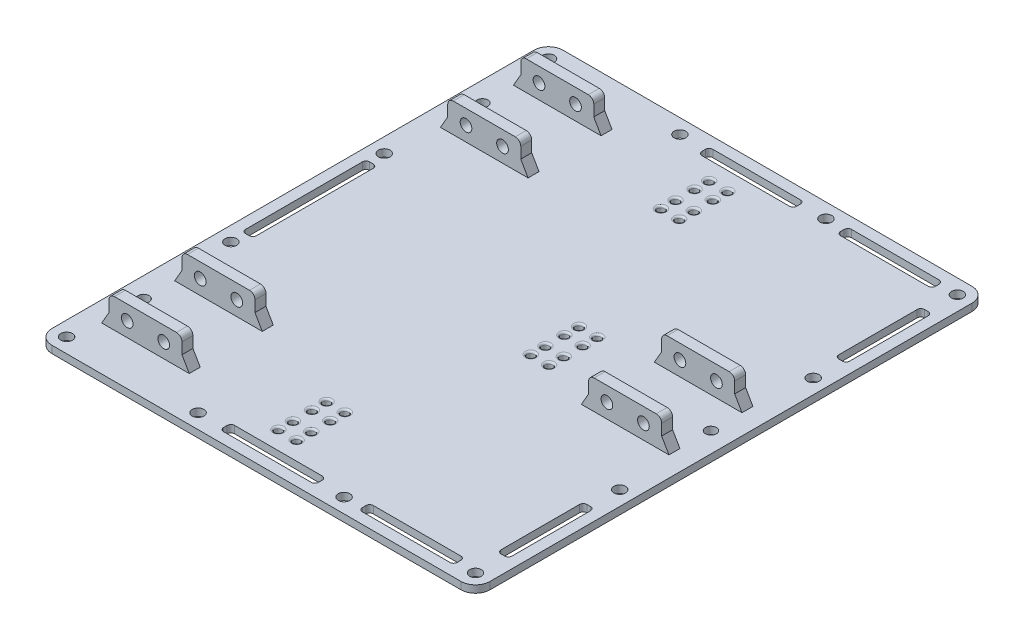
SolidWorks part; units mm, degrees
ref_plane "Front Plane" through (0, 0, 0) normal (0, 0, 1) x (1, 0, 0)
ref_plane "Top Plane" through (0, 0, 0) normal (0, 1, 0) x (1, 0, 0)
ref_plane "Right Plane" through (0, 0, 0) normal (1, 0, 0) x (0, 0, -1)
sketch "Sketch1" plane through (0, 0, 0) normal (0, 1, 0) x (1, 0, 0)
  line L1 (-60, -70) -> (60, -70)
  line L2 (-60, -70) -> (-60, 70)
  line L3 (-60, 70) -> (60, 70)
  line L4 (60, -70) -> (60, 70)
  line L5 (-60, -70) -> (60, 70) construction
  line L6 (-60, 70) -> (60, -70) construction
  point P0 (0, 0)
  dimension "D1" = 120
  dimension "D2" = 140
extrude "Boss-Extrude1" add sketch "Sketch1" along normal blind 2
sketch "Sketch3" plane through (0, 2, 0) normal (0, 1, 0) x (1, 0, 0)
  line L0 (-60, -70) -> (60, -70) construction
  line L1 (-52.5, 57.9) -> (-32.5, 57.9)
  line L2 (-52.5, 57.9) -> (-52.5, 54.9)
  line L3 (-52.5, 54.9) -> (-32.5, 54.9)
  line L4 (-32.5, 57.9) -> (-32.5, 54.9)
  line L5 (-52.5, 37.9) -> (-32.5, 37.9)
  line L6 (-52.5, 37.9) -> (-52.5, 34.9)
  line L7 (-52.5, 34.9) -> (-32.5, 34.9)
  line L8 (-32.5, 37.9) -> (-32.5, 34.9)
  line L9 (-52.5, -34.9) -> (-32.5, -34.9)
  line L10 (-52.5, -34.9) -> (-52.5, -37.9)
  line L11 (-52.5, -37.9) -> (-32.5, -37.9)
  line L12 (-32.5, -34.9) -> (-32.5, -37.9)
  line L13 (-52.5, -54.9) -> (-32.5, -54.9)
  line L14 (-52.5, -54.9) -> (-52.5, -57.9)
  line L15 (-52.5, -57.9) -> (-32.5, -57.9)
  line L16 (-32.5, -54.9) -> (-32.5, -57.9)
  line L17 (32.5, 11.5) -> (52.5, 11.5)
  line L18 (32.5, 11.5) -> (32.5, 8.5)
  line L19 (32.5, 8.5) -> (52.5, 8.5)
  line L20 (52.5, 11.5) -> (52.5, 8.5)
  line L21 (32.5, -8.5) -> (52.5, -8.5)
  line L22 (32.5, -8.5) -> (32.5, -11.5)
  line L23 (32.5, -11.5) -> (52.5, -11.5)
  line L24 (52.5, -8.5) -> (52.5, -11.5)
  line L25 (-60, 70) -> (-60, -70) construction
  line L26 (60, 70) -> (-60, 70) construction
  line L27 (60, -70) -> (60, 70) construction
  dimension "D1" = 12.1
  dimension "D2" = 3
  dimension "D3" = 7.5
  dimension "D4" = 27.5
  dimension "D5" = 7.5
  dimension "D6" = 27.5
  dimension "D7" = 3
  dimension "D8" = 32.1
  dimension "D9" = 12.1
  dimension "D10" = 3
  dimension "D11" = 7.5
  dimension "D12" = 27.5
  dimension "D13" = 32.1
  dimension "D14" = 3
  dimension "D15" = 7.5
  dimension "D16" = 27.5
  dimension "D17" = 7.5
  dimension "D18" = 27.5
  dimension "D19" = 3
  dimension "D20" = 8.5
  dimension "D21" = 7.5
  dimension "D22" = 27.5
  dimension "D23" = 3
  dimension "D24" = 8.5
extrude "Boss-Extrude2" add sketch "Sketch3" along normal blind 8
sketch "Sketch4" plane through (0, 0, 57.9) normal (0, 0, 1) x (1, 0, 0)
  line L0 (-60, 2) -> (60, 2) construction
  line L1 (-60, 2) -> (-60, 0) construction
  line L2 (60, 2) -> (60, 0) construction
  line L3 (32.5, 2) -> (52.5, 2) construction
  circle A0 centre (-47.5, 6) radius 1.6
  circle A1 centre (-37.5, 6) radius 1.6
  circle A2 centre (37.5, 6) radius 1.6
  circle A3 centre (47.5, 6) radius 1.6
  dimension "D3" = 3.2
  dimension "D6" = 3.2
  dimension "D7" = 3.2
  dimension "D12" = 3.2
  dimension "D1" = 4
  dimension "D2" = 12.5
  dimension "D4" = 10
  dimension "D5" = 4
  dimension "D8" = 12.5
  dimension "D9" = 4
  dimension "D10" = 4
  dimension "D11" = 22.5
extrude "Cut-Extrude2" cut sketch "Sketch4" against normal through all
sketch "Sketch5" plane through (0, 2, 0) normal (0, 1, 0) x (1, 0, 0)
  line L0 (-60, -70) -> (60, -70) construction
  line L1 (-60, 70) -> (-60, -70) construction
  line L2 (60, -70) -> (60, 70) construction
  line L3 (60, 70) -> (-60, 70) construction
  circle A0 centre (-56, -66) radius 1.6
  circle A1 centre (56, -66) radius 1.6
  circle A2 centre (56, 66) radius 1.6
  circle A3 centre (-56, 66) radius 1.6
  circle A6 centre (-56, -21) radius 1.6
  circle A7 centre (-56, 21) radius 1.6
  circle A8 centre (-20, -66) radius 1.6
  circle A9 centre (-20, 66) radius 1.6
  circle A10 centre (20, -66) radius 1.6
  circle A11 centre (20, 66) radius 1.6
  circle A12 centre (56, -26.5) radius 1.6
  circle A13 centre (56, 26.5) radius 1.6
  dimension "D1" = 3.2
  dimension "D2" = 3.2
  dimension "D3" = 3.2
  dimension "D6" = 3.2
  dimension "D13" = 40
  dimension "D16" = 4
  dimension "D20" = 3.2
  dimension "D22" = 3.2
  dimension "D25" = 3.2
  dimension "D28" = 3.2
  dimension "D31" = 3.2
  dimension "D7" = 3.2
  dimension "D10" = 3.2
  dimension "D29" = 3.2
  dimension "D4" = 4
  dimension "D5" = 4
  dimension "D8" = 4
  dimension "D9" = 4
  dimension "D11" = 4
  dimension "D12" = 4
  dimension "D14" = 40
  dimension "D15" = 40
  dimension "D17" = 4
  dimension "D19" = 4
  dimension "D21" = 4
  dimension "D23" = 49
  dimension "D24" = 49
  dimension "D26" = 43.5
  dimension "D32" = 40
  dimension "D33" = 43.5
  dimension "D34" = 4
extrude "Cut-Extrude3" cut sketch "Sketch5" against normal through all
fillet "Fillet1" radius 4 4 edges at (60, 1, -70) (-60, 1, -70) (-60, 1, 70) (60, 1, 70)
sketch "Sketch6" plane through (0, 0, 0) normal (0, -1, 0) x (1, 0, 0)
  line L0 (0, 55) -> (0, 49.8) construction
  line L1 (0, 0) -> (-60, 0) construction
  line L2 (56, -70) -> (-56, -70) construction
  line L3 (-5, -49.8) -> (-5, -55) construction
  line L4 (-60, -66) -> (-60, 66) construction
  line L5 (0, -49.8) -> (0, -55) construction
  line L6 (-5, 49.8) -> (-5, 55) construction
  line L7 (60, 66) -> (60, -66) construction
  line L8 (-56, 70) -> (56, 70) construction
  line L9 (16.75, 2.6) -> (16.75, -2.6) construction
  line L10 (11.75, 2.6) -> (11.75, -2.6) construction
  circle A0 centre (0, 59) radius 1
  circle A1 centre (0, 49.8) radius 1
  circle A8 centre (0, 45.8) radius 1
  circle A9 centre (0, 55) radius 1
  circle A10 centre (0, 45.8) radius 1
  circle A11 centre (0, 55) radius 1
  circle A13 centre (0, -49.8) radius 1
  circle A14 centre (0, -55) radius 1
  circle A16 centre (0, -45.8) radius 1
  circle A17 centre (0, -59) radius 1
  circle A24 centre (-5, -49.8) radius 1
  circle A25 centre (-5, -55) radius 1
  circle A26 centre (-5, -45.8) radius 1
  circle A27 centre (-5, -59) radius 1
  circle A28 centre (-5, 59) radius 1
  circle A29 centre (-5, 45.8) radius 1
  circle A30 centre (-5, 55) radius 1
  circle A31 centre (-5, 49.8) radius 1
  circle A32 centre (16.75, 2.6) radius 1
  circle A33 centre (16.75, -2.6) radius 1
  circle A34 centre (16.75, 6.6) radius 1
  circle A35 centre (16.75, -6.6) radius 1
  circle A36 centre (11.75, 2.6) radius 1
  circle A37 centre (11.75, -2.6) radius 1
  circle A38 centre (11.75, 6.6) radius 1
  circle A39 centre (11.75, -6.6) radius 1
  point P6 (16.75, 0)
  point P8 (0, -52.4)
  point P9 (0, 52.4)
  point P49 (-5, -52.4)
  point P77 (0, 0)
  point P78 (11.75, 0)
  point P87 (0, 0)
  dimension "D1" = 2
  dimension "D2" = 2
  dimension "D10" = 43.25
  dimension "D14" = 2
  dimension "D16" = 2
  dimension "D18" = 2
  dimension "D25" = 17.6
  dimension "D26" = 2
  dimension "D27" = 2
  dimension "D28" = 2
  dimension "D29" = 2
  dimension "D30" = 60
  dimension "D37" = 2
  dimension "D49" = 2
  dimension "D50" = 2
  dimension "D51" = 2
  dimension "D6" = 70
  dimension "D11" = 70
  dimension "D12" = 4
  dimension "D13" = 4
  dimension "D15" = 4
  dimension "D17" = 4
  dimension "D21" = 60
  dimension "D22" = 60
  dimension "D23" = 17.6
  dimension "D24" = 4
  dimension "D31" = 5.2
  dimension "D32" = 17.6
  dimension "D33" = 55
  dimension "D34" = 4
  dimension "D35" = 5.2
  dimension "D36" = 4
  dimension "D38" = 5
  dimension "D39" = 11
  dimension "D47" = 4
  dimension "D48" = 5.2
extrude "Cut-Extrude4" cut sketch "Sketch6" against normal blind 55 contours A16 | A13 | A14 | A17 | A0 | A9 | A1 | A27 | A24 | A26 | A29 | A31 | A30 | A28 | A8 | A35 | A33 | A32 | A34 | A38 | A36 | A37 | A39 | A25 region at (0, 0, -45.8)
chamfer "Chamfer1" distance 2 angle 60 12 edges at (-32.5, 2, -56.4) (-52.5, 2, -56.4) (-52.5, 2, -36.4) (-32.5, 2, -36.4) (52.5, 2, -10) (32.5, 2, -10) (32.5, 2, 10) (52.5, 2, 10) (-32.5, 2, 36.4) (-52.5, 2, 36.4) (-52.5, 2, 56.4) (-32.5, 2, 56.4) first distance on face at (-5, 2, -46.8)
sketch "Sketch8" plane through (0, 2, 0) normal (0, 1, 0) x (1, 0, 0)
  line L0 (-60, 66) -> (-60, -66) construction
  line L1 (-56, 17) -> (-55, 17)
  line L2 (-57, 16) -> (-57, -16)
  line L3 (-56, -17) -> (-55, -17)
  line L4 (-54, 16) -> (-54, -16)
  line L5 (-12, -64) -> (12, -64)
  line L6 (-13, -65) -> (-13, -66)
  line L7 (-12, -67) -> (12, -67)
  line L8 (13, -65) -> (13, -66)
  line L9 (55, -34.5) -> (56, -34.5)
  line L10 (54, -35.5) -> (54, -57)
  line L11 (55, -58) -> (56, -58)
  line L12 (57, -35.5) -> (57, -57)
  line L13 (55, 58) -> (56, 58)
  line L14 (54, 57) -> (54, 35.5)
  line L15 (55, 34.5) -> (56, 34.5)
  line L16 (57, 57) -> (57, 35.5)
  line L21 (-56, -70) -> (56, -70) construction
  line L22 (60, -66) -> (60, 66) construction
  line L23 (56, 70) -> (-56, 70) construction
  line L24 (0, 0) -> (60, 0) construction
  line L25 (26, -64) -> (50, -64)
  line L26 (25, -65) -> (25, -66)
  line L27 (26, -67) -> (50, -67)
  line L28 (51, -65) -> (51, -66)
  line L29 (51, 65) -> (51, 66)
  line L30 (26, 67) -> (50, 67)
  line L31 (25, 65) -> (25, 66)
  line L32 (26, 64) -> (50, 64)
  line L33 (13, 65) -> (13, 66)
  line L34 (-12, 67) -> (12, 67)
  line L35 (-13, 65) -> (-13, 66)
  line L36 (-12, 64) -> (12, 64)
  arc A0 (54, 35.5) -> (55, 34.5) centre (55, 35.5) ccw
  arc A1 (56, 34.5) -> (57, 35.5) centre (56, 35.5) ccw
  arc A2 (56, 58) -> (57, 57) centre (56, 57) cw
  arc A3 (55, 58) -> (54, 57) centre (55, 57) ccw
  arc A4 (56, -34.5) -> (57, -35.5) centre (56, -35.5) cw
  arc A5 (55, -34.5) -> (54, -35.5) centre (55, -35.5) ccw
  arc A6 (56, -58) -> (57, -57) centre (56, -57) ccw
  arc A7 (54, -57) -> (55, -58) centre (55, -57) ccw
  arc A8 (25, -66) -> (26, -67) centre (26, -66) ccw
  arc A9 (50, -64) -> (51, -65) centre (50, -65) cw
  arc A10 (50, -67) -> (51, -66) centre (50, -66) ccw
  arc A11 (26, -64) -> (25, -65) centre (26, -65) ccw
  arc A12 (-13, -66) -> (-12, -67) centre (-12, -66) ccw
  arc A13 (12, -64) -> (13, -65) centre (12, -65) cw
  arc A14 (12, -67) -> (13, -66) centre (12, -66) ccw
  arc A15 (-12, -64) -> (-13, -65) centre (-12, -65) ccw
  arc A16 (-55, -17) -> (-54, -16) centre (-55, -16) ccw
  arc A17 (-57, -16) -> (-56, -17) centre (-56, -16) ccw
  arc A18 (-55, 17) -> (-54, 16) centre (-55, 16) cw
  arc A19 (-57, 16) -> (-56, 17) centre (-56, 16) cw
  arc A20 (-12, 64) -> (-13, 65) centre (-12, 65) cw
  arc A21 (12, 67) -> (13, 66) centre (12, 66) cw
  arc A22 (12, 64) -> (13, 65) centre (12, 65) ccw
  arc A23 (-13, 66) -> (-12, 67) centre (-12, 66) cw
  arc A24 (26, 64) -> (25, 65) centre (26, 65) cw
  arc A25 (50, 67) -> (51, 66) centre (50, 66) cw
  arc A26 (50, 64) -> (51, 65) centre (50, 65) ccw
  arc A27 (25, 66) -> (26, 67) centre (26, 66) cw
  point P32 (54, 34.5)
  point P36 (57, 34.5)
  point P39 (57, 58)
  point P44 (57, -34.5)
  point P49 (57, -58)
  point P52 (54, -58)
  point P55 (25, -67)
  point P60 (51, -67)
  point P63 (25, -64)
  point P66 (-13, -67)
  point P71 (13, -67)
  point P74 (-13, -64)
  point P79 (-57, -17)
  point P82 (-54, 17)
  point P85 (-57, 17)
  point P110 (-13, 64)
  point P111 (13, 67)
  point P112 (-13, 67)
  point P113 (25, 64)
  point P114 (51, 67)
  point P115 (25, 67)
  dimension "D21" = 1
  dimension "D1" = 26
  dimension "D2" = 3
  dimension "D3" = 47
  dimension "D4" = 3
  dimension "D5" = 23.5
  dimension "D6" = 12
  dimension "D7" = 3
  dimension "D8" = 3
  dimension "D9" = 12
  dimension "D10" = 23.5
  dimension "D11" = 3
  dimension "D12" = 3
  dimension "D13" = 26
  dimension "D14" = 9
  dimension "D15" = 3
  dimension "D16" = 3
  dimension "D17" = 34
  dimension "D18" = 53
  dimension "D19" = 3
  dimension "D20" = 3
extrude "Cut-Extrude5" cut sketch "Sketch8" against normal through all
fillet "Fillet2" radius 1.5 12 edges at (52.5, 10, -10) (32.5, 10, -10) (52.5, 10, 10) (32.5, 10, 10) (-32.5, 10, -56.4) (-52.5, 10, -56.4) (-32.5, 10, -36.4) (-52.5, 10, -36.4) (-32.5, 10, 36.4) (-52.5, 10, 36.4) (-32.5, 10, 56.4) (-52.5, 10, 56.4)
fillet "Fillet3" radius 0.5 24 edges at (-5, 2, -60) (0, 2, -60) (0, 2, -56) (-5, 2, -56) (-5, 2, -50.8) (0, 2, -50.8) (0, 2, -46.8) (-5, 2, -46.8) (11.75, 2, 5.6) (11.75, 2, 1.6) (11.75, 2, -3.6) (11.75, 2, -7.6) (16.75, 2, -7.6) (16.75, 2, -3.6) (16.75, 2, 1.6) (16.75, 2, 5.6) (-5, 2, 44.8) (0, 2, 44.8) (0, 2, 48.8) (-5, 2, 48.8) (0, 2, 54) (-5, 2, 54) (0, 2, 58) (-5, 2, 58)
sketch "Sketch9" plane through (0, 2, 0) normal (0, 1, 0) x (1, 0, 0)
  line L0 (54.5, -8.5) -> (54.5, 8.5)
  line L1 (-54.5, 54.9) -> (-54.5, 37.9)
  line L2 (-54.5, -54.9) -> (-54.5, -37.9)
  circle A0 centre (54.5, 0) radius 1.5
  circle A1 centre (-54.5, 46.4) radius 1.5
  circle A2 centre (-54.5, -46.4) radius 1.5
  dimension "D1" = 3
  dimension "D2" = 3
  dimension "D3" = 3
extrude "Cut-Extrude6" cut sketch "Sketch9" against normal through all contours L0 A0 | L0 A0 | L1 A1 | L1 A1 | L2 A2 | L2 A2 region at (53.8634, 2, 0) region at (55.1366, 2, 0) region at (-53.8634, 2, -46.4) region at (-55.1366, 2, -46.4) region at (-55.1366, 2, 46.4) region at (-53.8634, 2, 46.4)
